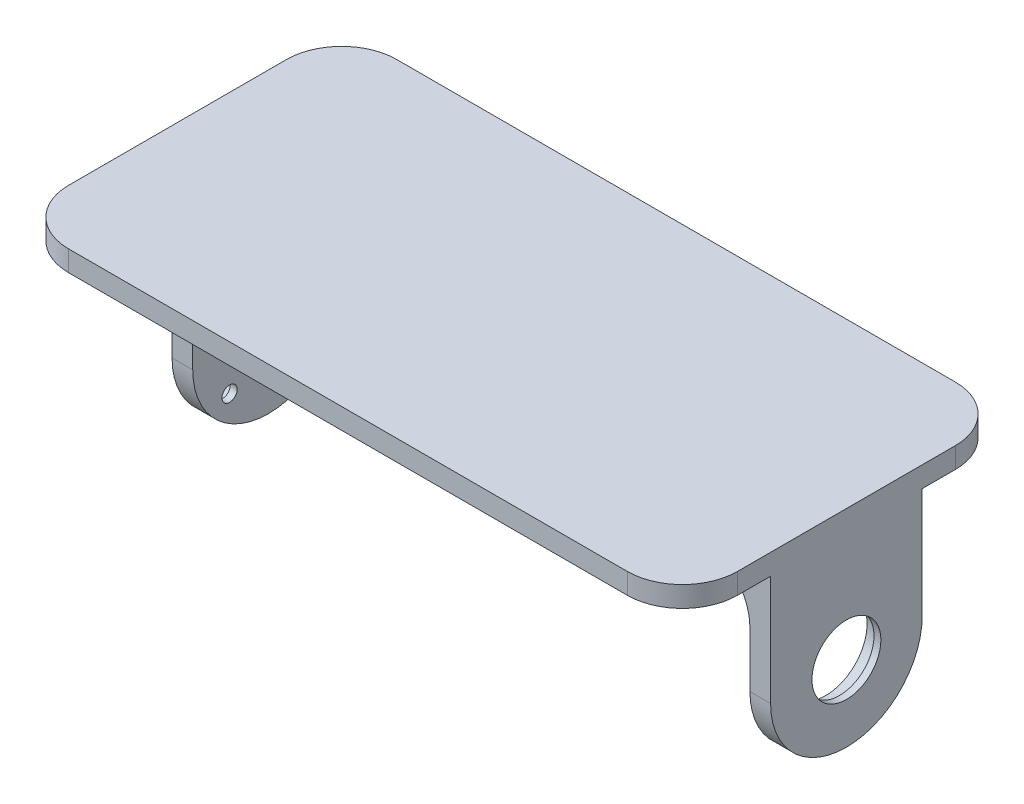
SolidWorks part; units mm, degrees
ref_plane "Front Plane" through (0, 0, 0) normal (0, 0, 1) x (1, 0, 0)
ref_plane "Top Plane" through (0, 0, 0) normal (0, 1, 0) x (1, 0, 0)
ref_plane "Right Plane" through (0, 0, 0) normal (1, 0, 0) x (0, 0, -1)
sketch "Sketch1" plane through (0, 0, 0) normal (0, 1, 0) x (1, 0, 0)
  line L5 (-39.0891, 0) -> (41.7609, 0) construction
  line L6 (-42.6234, -11) -> (-38.6234, -11)
  line L9 (-38.6234, -11) -> (-42.6234, -11)
  line L10 (-42.0891, 11) -> (-42.0891, -11)
  line L14 (44.7609, 11) -> (44.7609, -11)
  line L15 (23.9842, 12.3255) -> (24.0296, 12.3942) construction
  line L16 (-42.0891, 11) -> (-39.0891, 11)
  line L17 (-42.0891, 11) -> (-42.0891, -11)
  line L18 (-42.0891, -11) -> (-39.0891, -11)
  line L19 (-39.0891, 11) -> (-39.0891, -11)
  line L20 (44.7609, 11) -> (41.7609, 11)
  line L21 (44.7609, 11) -> (44.7609, -11)
  line L22 (44.7609, -11) -> (41.7609, -11)
  line L23 (41.7609, 11) -> (41.7609, -11)
  line L25 (-42.0891, 11) -> (-42.0891, -11)
  line L27 (-52.2891, 11) -> (-52.2891, -11)
  line L29 (44.7609, 11) -> (44.7609, -11)
  line L31 (44.7609, 23.8) -> (44.7609, -11)
  line L34 (44.7609, 23.8) -> (-52.2891, 23.8)
  line L35 (-52.2891, 11) -> (-52.2891, 23.8)
  line L36 (-52.2891, -11) -> (-52.2891, -23.8)
  line L37 (-52.2891, -23.8) -> (44.7609, -23.8)
  line L38 (44.7609, -11) -> (44.7609, -23.8)
  arc A1 (23.9842, 12.3255) -> (23.8207, 12.4147) centre (23.3776, 11.4078) ccw
  point P0 (-3.7641, 0)
  point P3 (-42.0891, 0)
  point P7 (-52.2891, 0)
  point P15 (-3.7641, -23.8)
  point P29 (-39.0891, 0)
  point P30 (41.7609, 0)
  dimension "D5" = 97.05
  dimension "D9" = 2.2
  dimension "D1" = 86.85
  dimension "D2" = 47.6
  dimension "D3" = 3
  dimension "D4" = 22
extrude "Boss-Extrude1" add sketch "Sketch1" along normal blind 3 contours L34 L35 L27 L36 L37 L38 L31
sketch "Sketch5" plane through (0, 0, 0) normal (0, -1, 0) x (1, 0, 0)
  line L1 (-42.0891, 11) -> (-39.0891, 11)
  line L2 (-42.0891, 11) -> (-42.0891, -11)
  line L3 (-42.0891, -11) -> (-39.0891, -11)
  line L4 (-39.0891, 11) -> (-39.0891, -11)
  line L5 (41.7609, 11) -> (44.7609, 11)
  line L6 (41.7609, 11) -> (41.7609, -11)
  line L7 (41.7609, -11) -> (44.7609, -11)
  line L8 (44.7609, 11) -> (44.7609, -11)
  dimension "D2" = 3
extrude "Boss-Extrude2" add sketch "Sketch5" along normal blind 27
sketch "Sketch2" plane through (-42.0891, 0, 0) normal (-1, 0, 0) x (0, 0, 1)
  line L0 (0, -16) -> (-5.6569, -21.6569) construction
  line L2 (11, -27) -> (-11, -27) construction
  circle A2 centre (0, -16) radius 3
  circle A3 centre (-5.6569, -21.6569) radius 1.1
  dimension "D1" = 8
  dimension "D5" = 11
  dimension "D2" = 6
  dimension "D3" = 2.2
  dimension "D4" = 45
extrude "Cut-Extrude1" cut sketch "Sketch2" against normal up to surface (3 mm away) contours A2 | A3 region at (-42.0891, -16, 0) up to face at (-39.0891, -13.5, 0)
pattern_circular "CirPattern1" count 4 over 360 about axis through (-42.0891, -16, 0) along (-1, 0, 0) of "Cut-Extrude1"
fillet "Fillet3" radius 11 4 edges at (-40.5891, -27, -11) (-40.5891, -27, 11) (43.2609, -27, -11) (43.2609, -27, 11)
sketch "Sketch6" plane through (-42.0891, 0, 0) normal (-1, 0, 0) x (0, 0, 1)
  circle A0 centre (5.6569, -10.3431) radius 2
  circle A1 centre (5.6569, -10.3431) radius 1.1 construction
  dimension "D1" = 4
extrude "Cut-Extrude5" cut sketch "Sketch6" against normal offset from surface (2 mm away) 1 up to face at (-39.0891, -10.3431, -4.5569)
pattern_circular "CirPattern2" count 4 over 360 about axis through (-42.0891, -16, 0) along (-1, 0, 0) of "Cut-Extrude5"
sketch "Sketch7" plane through (41.7609, 0, 0) normal (-1, 0, 0) x (0, 0, 1)
  circle A1 centre (0, -16) radius 3 construction
  circle A2 centre (0, -16) radius 5
  circle A3 centre (0, -16) radius 6
  dimension "D2" = 12
  dimension "D3" = 1
extrude "Cut-Extrude6" cut sketch "Sketch7" against normal up to surface (3 mm away) contours A2 region at (41.7609, -16, 0) up to face at (44.7609, -6.3951, 0)
extrude "Cut-Extrude7" cut sketch "Sketch7<5>" against normal offset from surface (2 mm away) 1 up to face at (44.7609, -16, -5)
sketch "Sketch7<5>" plane through (41.7609, 0, 0) normal (-1, 0, 0) x (0, 0, 1) same geometry as "Sketch7"
fillet "Fillet4" radius 8 7 edges at (-42.0891, 0, 0) (41.7609, 0, 0) (-39.0891, 0, 0) (-52.2891, 1.5, 23.8) (44.7609, 1.5, 23.8) (44.7609, 1.5, -23.8) (-52.2891, 1.5, -23.8)
